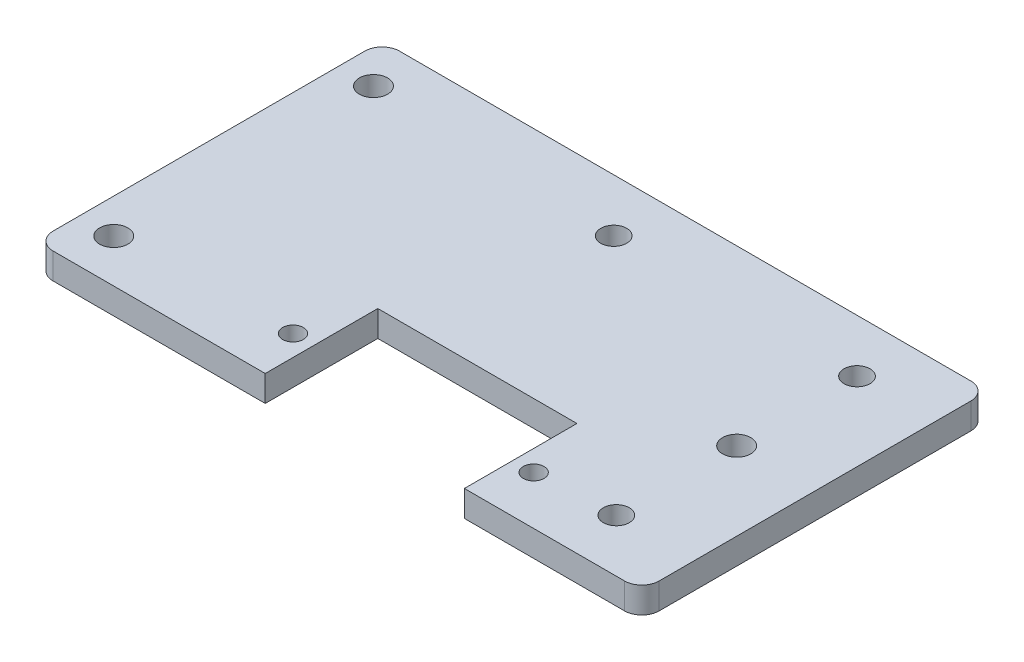
SolidWorks part; units mm, degrees
ref_plane "Front Plane" through (0, 0, 0) normal (0, 0, 1) x (1, 0, 0)
ref_plane "Top Plane" through (0, 0, 0) normal (0, 1, 0) x (1, 0, 0)
ref_plane "Right Plane" through (0, 0, 0) normal (1, 0, 0) x (0, 0, -1)
sketch "Sketch1" plane through (0, 0, 0) normal (0, 1, 0) x (1, 0, 0)
  line L1 (-35, 20) -> (35, 20)
  line L2 (-35, 20) -> (-35, -20)
  line L3 (-35, -20) -> (35, -20)
  line L4 (35, 20) -> (35, -20)
  line L5 (-35, 20) -> (35, -20) construction
  line L6 (-35, -20) -> (35, 20) construction
  point P0 (0, 0)
  dimension "D1" = 70
  dimension "D2" = 40
extrude "Boss-Extrude1" add sketch "Sketch1" along normal blind 3
hole_wizard "Ø3.0mm Dowel Hole1" positions "Sketch2" profile "Sketch3" hole size "Ø3.0" standard "ANSI Metric" end condition through all
sketch "Sketch2" plane through (0, 3, 0) normal (0, 1, 0) x (1, 0, 0)
  line L2 (35, -20) -> (35, 20) construction
  line L3 (-35, -20) -> (35, -20) construction
  point P0 (-2.15, 13.9)
  point P2 (25.95, 13.9)
  point P6 (25.95, -13.9)
  dimension "D3" = 27.8
  dimension "D1" = 37.15
  dimension "D2" = 9.05
  dimension "D4" = 6.1
sketch "Sketch3" plane through (-2.15, 3, -13.9) normal (1, 0, 0) x (0, 0, 1)
  line L0 (0, 0) -> (0, 3)
  line L1 (0, 3) -> (1.5, 3)
  line L2 (1.5, 3) -> (1.5, 0)
  line L5 (1.5, 0) -> (0, 0)
  line L11 (0, -6.35) -> (0, 107.95) construction
  dimension "Thru Hole Dia." = 3
  dimension "Thru Hole Depth" = 3
hole_wizard "#4 Clearance Hole1" positions "Sketch4" profile "Sketch5" hole size "#4" standard "ANSI Inch" end condition through all
sketch "Sketch4" plane through (0, 3, 0) normal (0, 1, 0) x (1, 0, 0)
  line L0 (-35, 20) -> (-35, -20) construction
  line L1 (-35, -20) -> (35, -20) construction
  line L2 (35, 20) -> (-35, 20) construction
  line L4 (35, -20) -> (35, 20) construction
  point P0 (-31, 15)
  point P2 (-31, -15)
  point P11 (25.95, 0)
  dimension "D1" = 4
  dimension "D2" = 4
  dimension "D3" = 5
  dimension "D4" = 5
  dimension "D5" = 9.05
sketch "Sketch5" plane through (-31, 3, -15) normal (1, 0, 0) x (0, 0, 1)
  line L0 (0, 0) -> (0, 3)
  line L1 (0, 3) -> (1.6319, 3)
  line L2 (1.6319, 3) -> (1.6319, 0)
  line L5 (1.6319, 0) -> (0, 0)
  line L11 (0, -6.35) -> (0, 107.95) construction
  dimension "Thru Hole Dia." = 3.2639
  dimension "Thru Hole Depth" = 3
hole_wizard "M2 Clearance Hole1" positions "Sketch6" profile "Sketch7" hole size "M2" standard "ANSI Metric" end condition through all
sketch "Sketch6" plane through (0, 3, 0) normal (0, 1, 0) x (1, 0, 0)
  line L0 (-35, -20) -> (35, -20) construction
  line L1 (35, -20) -> (35, 20) construction
  point P0 (-10.9, -14.4)
  point P2 (16.9, -14.4)
  dimension "D1" = 27.8
  dimension "D2" = 5.6
  dimension "D3" = 18.1
sketch "Sketch7" plane through (-10.9, 3, 14.4) normal (1, 0, 0) x (0, 0, 1)
  line L0 (0, 0) -> (0, 3)
  line L1 (0, 3) -> (1.2, 3)
  line L2 (1.2, 3) -> (1.2, 0)
  line L5 (1.2, 0) -> (0, 0)
  line L11 (0, -6.35) -> (0, 107.95) construction
  dimension "Thru Hole Dia." = 2.4
  dimension "Thru Hole Depth" = 3
sketch "Sketch8" plane through (0, 3, 0) normal (0, 1, 0) x (1, 0, 0)
  line L0 (-35, -20) -> (35, -20) construction
  line L1 (-8.5, -20) -> (14.5, -20)
  line L2 (-8.5, -20) -> (-8.5, -7)
  line L3 (-8.5, -7) -> (14.5, -7)
  line L4 (14.5, -20) -> (14.5, -7)
  circle A0 centre (16.9, -14.4) radius 1.2 construction
  point P6 (3, -7)
  dimension "D1" = 13
  dimension "D2" = 23
  dimension "D3" = 13.9
extrude "Cut-Extrude1" cut sketch "Sketch8" against normal blind 10
fillet "Fillet1" radius 2 4 edges at (35, 1.5, -20) (35, 1.5, 20) (-35, 1.5, 20) (-35, 1.5, -20)
equation "\"D4@Sketch2\"=(40-\"D3@Sketch2\")/2"
equation "\"D4@Sketch4\"=\"D3@Sketch4\""
equation "\"D2@Sketch4\"=\"D1@Sketch4\""
equation "\"D3@Sketch6\"=9.05*2"
